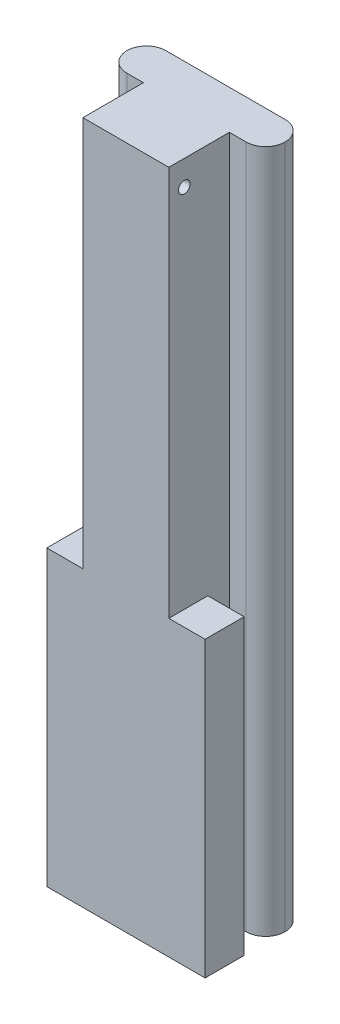
SolidWorks part; units mm, degrees
ref_plane "Front Plane" through (0, 0, 0) normal (0, 0, 1) x (1, 0, 0)
ref_plane "Top Plane" through (0, 0, 0) normal (0, 1, 0) x (1, 0, 0)
ref_plane "Right Plane" through (0, 0, 0) normal (1, 0, 0) x (0, 0, -1)
sketch "Sketch1" plane through (0, 0, 0) normal (0, 1, 0) x (1, 0, 0)
  line L1 (0, 0) -> (205.7636, 0)
  line L2 (0, 0) -> (0, -129.4551)
  line L3 (0, -129.4551) -> (205.7636, -129.4551)
  line L4 (205.7636, 0) -> (205.7636, -129.4551)
extrude "Boss-Extrude1" add sketch "Sketch1" along normal blind 889.508 contours L4 L1 L2 L3 | L2 L1 L4 L3 region at (102.8818, 0, 64.7275)
sketch "Sketch2" plane through (0, 889.508, 0) normal (0, 1, 0) x (1, 0, 0)
  line L1 (0, 0) -> (0, -129.4551) construction
  line L2 (0, -50.7596) -> (34.2281, -50.7596)
  line L3 (34.2281, -50.7596) -> (34.2281, -78.6955)
  line L4 (34.2281, -78.6955) -> (0, -78.6955)
  line L5 (0, -78.6955) -> (0, -50.7596)
extrude "Cut-Extrude1" cut sketch "Sketch2" against normal blind 1151.636 contours L2 L3 L4 L5
sketch "Sketch3" plane through (0, 889.508, 0) normal (0, 1, 0) x (1, 0, 0)
  line L0 (205.7636, -50.7596) -> (171.5355, -50.7596)
  line L1 (205.7636, 0) -> (205.7636, -129.4551) construction
  line L2 (171.5355, -50.7596) -> (171.5355, -78.6955)
  line L3 (171.5355, -78.6955) -> (205.7636, -78.6955)
  line L4 (205.7636, -78.6955) -> (205.7636, -50.7596)
extrude "Cut-Extrude2" cut sketch "Sketch3" against normal blind 1331.214 contours L4 L0 L2 L3
fillet "Fillet3" radius 25.4 1 edges at (0, 444.754, 0)
fillet "Fillet4" radius 25.4 1 edges at (205.7636, 444.754, 0)
fillet "Fillet5" radius 25.4 1 edges at (205.7636, 444.754, 50.7596)
fillet "Fillet7" radius 25.4 1 edges at (0, 444.754, 50.7596)
sketch "Sketch4" plane through (0, 889.508, 0) normal (0, 1, 0) x (1, 0, 0)
  line L0 (34.2281, -50.7596) -> (46.8783, -50.7596)
  line L1 (34.2281, -78.6955) -> (46.8783, -78.6955)
  line L2 (46.8783, -78.6955) -> (46.8783, -50.7596)
  line L3 (34.2281, -50.7596) -> (34.2281, -78.6955)
extrude "Boss-Extrude3" add sketch "Sketch4" against normal blind 874.268 contours L3 L1 L2 L0
sketch "Sketch5" plane through (0, 889.508, 0) normal (0, 1, 0) x (1, 0, 0)
  line L0 (34.2281, -50.7596) -> (46.8495, -50.7596)
  line L1 (46.8495, -50.7596) -> (46.8495, -78.6955)
  line L2 (46.8495, -78.6955) -> (34.2281, -78.6955)
  line L3 (34.2281, -78.6955) -> (34.2281, -50.7596)
extrude "Cut-Extrude5" cut sketch "Sketch5" against normal blind 1063.752 contours L3 L0 L1 L2
sketch "Sketch6" plane through (0, 889.508, 0) normal (0, 1, 0) x (1, 0, 0)
  line L0 (171.5355, -50.7596) -> (158.6218, -50.7596)
  line L1 (158.6218, -50.7596) -> (158.6218, -78.6955)
  line L2 (158.6218, -78.6955) -> (171.5355, -78.6955)
  line L3 (171.5355, -50.7596) -> (171.5355, -78.6955) construction
  line L4 (171.5355, -78.6955) -> (171.5355, -50.7596)
extrude "Cut-Extrude6" cut sketch "Sketch6" against normal blind 1244.346 contours L4 L0 L1 L2
sketch "Sketch8" plane through (0, 889.508, 0) normal (0, 1, 0) x (1, 0, 0)
  line L0 (46.8495, -78.6955) -> (46.8495, -129.4551)
  line L1 (0, -129.4551) -> (205.7636, -129.4551) construction
  line L2 (46.8495, -129.4551) -> (0, -129.4551)
  line L3 (0, -129.4551) -> (0, -78.6955)
  line L4 (0, -78.6955) -> (46.8495, -78.6955)
extrude "Cut-Extrude7" cut sketch "Sketch8" against normal blind 508 contours L4 L0 L2 L3
sketch "Sketch9" plane through (0, 889.508, 0) normal (0, 1, 0) x (1, 0, 0)
  line L0 (158.6218, -78.6955) -> (158.6218, -129.4551)
  line L1 (46.8495, -129.4551) -> (205.7636, -129.4551) construction
  line L2 (158.6218, -129.4551) -> (205.7636, -129.4551)
  line L3 (205.7636, -129.4551) -> (205.7636, -78.6955)
  line L4 (205.7636, -78.6955) -> (158.6218, -78.6955)
extrude "Cut-Extrude8" cut sketch "Sketch9" against normal blind 508 contours L4 L0 L2 L3
sketch "Sketch10" plane through (46.8495, 0, 0) normal (-1, 0, 0) x (0, 0, 1)
  circle A0 centre (109.3679, 857.0269) radius 7.6589
extrude "Cut-Extrude9" cut sketch "Sketch10" against normal blind 263.652 contours A0
